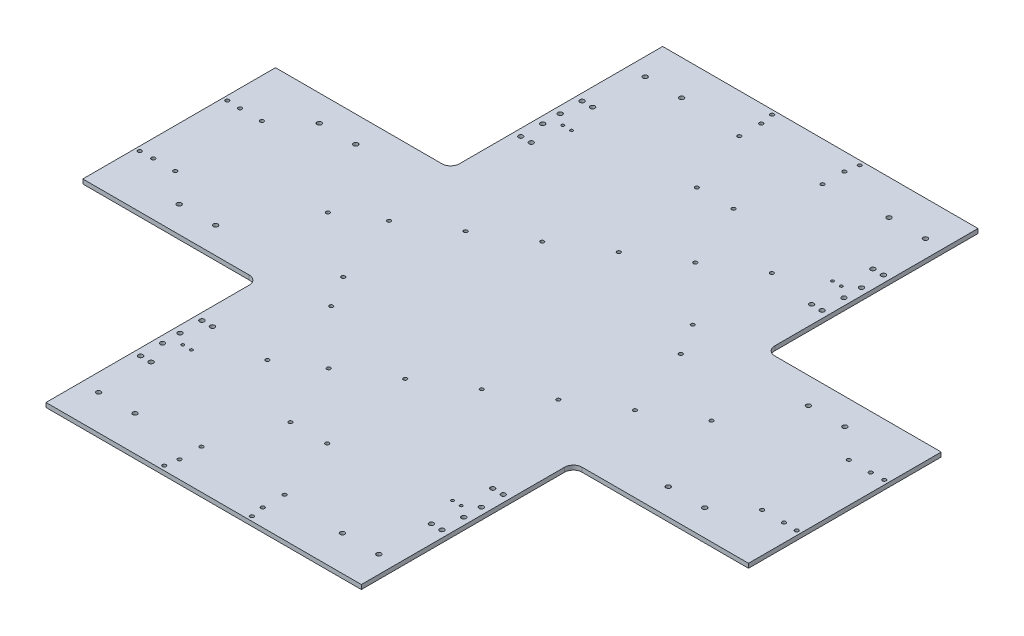
SolidWorks part; units mm, degrees
other "Markup1"
sketch "Sketch8"
material "3.0205 (EN-AW 1200)"
ref_plane "前视基准面" through (0, 0, 0) normal (0, 0, 1) x (1, 0, 0)
ref_plane "上视基准面" through (0, 0, 0) normal (0, 1, 0) x (1, 0, 0)
ref_plane "右视基准面" through (0, 0, 0) normal (1, 0, 0) x (0, 0, -1)
other "Configuration Table"
sketch "Sketch1" plane through (0, 0, 0) normal (0, 1, 0) x (1, 0, 0)
  line L0 (180, 352) -> (-180, 352)
  line L1 (-180, 352) -> (-180, 110)
  line L2 (-180, 110) -> (-380, 110)
  line L5 (-380, 110) -> (-380, -110)
  line L6 (0, 352) -> (0, -66.8675) construction
  line L7 (-380, 0) -> (131.0517, 0) construction
  line L8 (380, 110) -> (380, -110)
  line L11 (180, 110) -> (380, 110)
  line L12 (180, 352) -> (180, 110)
  line L13 (180, -352) -> (180, -110)
  line L14 (180, -110) -> (380, -110)
  line L19 (-180, -110) -> (-380, -110)
  line L20 (-180, -352) -> (-180, -110)
  line L21 (180, -352) -> (-180, -352)
  point P21 (380, 0)
  dimension "D1" = 180
  dimension "D2" = 200
  dimension "D3" = 110
  dimension "D4" = 242
extrude "Boss-Extrude1" add sketch "Sketch1" along normal blind 5
sketch "Sketch2" plane through (0, 5, 0) normal (0, 1, 0) x (1, 0, 0)
  line L3 (380, -110) -> (380, 110) construction
  line L4 (-56.7455, 0) -> (47.5165, 0) construction
  line L5 (0, 54.7142) -> (0, -64.2255) construction
  line L7 (180, 352) -> (-180, 352) construction
  circle A0 centre (360, 49.5) radius 2.125
  circle A1 centre (335, 49.5) radius 2.125
  circle A7 centre (335, -49.5) radius 2.125
  circle A8 centre (360, -49.5) radius 2.125
  circle A9 centre (-360, -49.5) radius 2.125
  circle A10 centre (-335, -49.5) radius 2.125
  circle A13 centre (-335, 49.5) radius 2.125
  circle A14 centre (-360, 49.5) radius 2.125
  circle A15 centre (47.5, 332) radius 2.125
  circle A16 centre (47.5, 307) radius 2.125
  circle A17 centre (-47.5, 307) radius 2.125
  circle A18 centre (-47.5, 332) radius 2.125
  circle A19 centre (-47.5, -332) radius 2.125
  circle A20 centre (-47.5, -307) radius 2.125
  circle A21 centre (47.5, -307) radius 2.125
  circle A22 centre (47.5, -332) radius 2.125
  dimension "D3" = 49.5
  dimension "D5" = 4.25
  dimension "D7" = 4.25
  dimension "D9" = 4.25
  dimension "D10" = 4.25
  dimension "D2" = 47.5
  dimension "D4" = 25
  dimension "D6" = 20
  dimension "20" = 20
  dimension "D13" = 25
extrude "Cut-Extrude1" cut sketch "Sketch2" against normal blind 3
sketch "Sketch4" plane through (0, 5, 0) normal (0, 1, 0) x (1, 0, 0)
  line L0 (-180, 352) -> (-180, 110) construction
  line L1 (180, 352) -> (-180, 352) construction
  line L2 (0, 46.9886) -> (0, -40.2904) construction
  line L3 (-35.103, 0) -> (92.4951, 0) construction
  line L5 (180, -352) -> (180, -110) construction
  circle A0 centre (-172, 182) radius 2.6
  circle A1 centre (-160, 182) radius 2.6
  circle A2 centre (-172, 207) radius 2.6
  circle A3 centre (-172, 227) radius 2.6
  circle A4 centre (-172, 252) radius 2.6
  circle A5 centre (-160, 252) radius 2.6
  circle A6 centre (160, 252) radius 2.6
  circle A7 centre (172, 252) radius 2.6
  circle A8 centre (172, 227) radius 2.6
  circle A9 centre (172, 207) radius 2.6
  circle A10 centre (160, 182) radius 2.6
  circle A11 centre (172, 182) radius 2.6
  circle A12 centre (172, -182) radius 2.6
  circle A13 centre (160, -182) radius 2.6
  circle A14 centre (172, -207) radius 2.6
  circle A15 centre (172, -227) radius 2.6
  circle A16 centre (172, -252) radius 2.6
  circle A17 centre (160, -252) radius 2.6
  circle A18 centre (-160, -252) radius 2.6
  circle A19 centre (-172, -252) radius 2.6
  circle A20 centre (-172, -227) radius 2.6
  circle A21 centre (-172, -207) radius 2.6
  circle A22 centre (-160, -182) radius 2.6
  circle A23 centre (-172, -182) radius 2.6
  circle A24 centre (159, -217) radius 1.6
  circle A25 centre (-159, -217) radius 1.6
  circle A26 centre (159, 217) radius 1.6
  circle A27 centre (-159, 217) radius 1.6
  circle A28 centre (149, -217) radius 1.6
  circle A29 centre (-149, -217) radius 1.6
  circle A30 centre (149, 217) radius 1.6
  circle A31 centre (-149, 217) radius 1.6
  dimension "D3" = 5.2
  dimension "D4" = 5.2
  dimension "D5" = 8
  dimension "D6" = 8
  dimension "D9" = 5.2
  dimension "D10" = 5.2
  dimension "D11" = 5.2
  dimension "D12" = 5.2
  dimension "D19" = 3.2
  dimension "D20" = 21
  dimension "D21" = 10
  dimension "D22" = 3.2
  dimension "D23" = 10
  dimension "D1" = 8
  dimension "D2" = 20
  dimension "D7" = 8
  dimension "D8" = 20
  dimension "D13" = 25
  dimension "D14" = 20
  dimension "D15" = 25
  dimension "D16" = 25
  dimension "D17" = 100
  dimension "D18" = 0
extrude "Cut-Extrude3" cut sketch "Sketch4" against normal blind 10
sketch "Sketch5" plane through (0, 5, 0) normal (0, 1, 0) x (1, 0, 0)
  line L0 (180, 352) -> (-180, 352) construction
  line L5 (-46.9195, 0) -> (66.6223, 0) construction
  line L6 (0, 59.0569) -> (0, -54.4849) construction
  line L10 (-380, 110) -> (-380, -110) construction
  circle A0 centre (-50, 347) radius 2.1
  circle A1 centre (50, 347) radius 2.1
  circle A2 centre (50, -347) radius 2.1
  circle A3 centre (-50, -347) radius 2.1
  circle A4 centre (-375, 50) radius 2.1
  circle A5 centre (-375, -50) radius 2.1
  circle A6 centre (375, -50) radius 2.1
  circle A7 centre (375, 50) radius 2.1
  dimension "D1" = 4.2
  dimension "D2" = 4.2
  dimension "D3" = 50
  dimension "D6" = 4.2
  dimension "D7" = 4.2
  dimension "5" = 5
  dimension "D4" = 50
  dimension "D5" = 50
  dimension "D8" = 50
  dimension "D9" = 5
  dimension "D10" = 5
extrude "Cut-Extrude4" cut sketch "Sketch5" against normal blind 10
fillet "Fillet1" radius 10 4 edges at (-180, 2.5, -110) (-180, 2.5, 110) (180, 2.5, 110) (180, 2.5, -110)
sketch "Sketch6" plane through (0, 5, 0) normal (0, 1, 0) x (1, 0, 0)
  line L0 (180, 352) -> (-180, 352) construction
  line L1 (-180, 352) -> (-180, 120) construction
  line L3 (0, 50.3702) -> (0, -42.7646) construction
  line L4 (-54.8568, 0) -> (91.2004, 0) construction
  line L5 (380, 110) -> (190, 110) construction
  line L6 (380, -110) -> (380, 110) construction
  circle A0 centre (-160, 312) radius 2.6
  circle A1 centre (-118.4, 312) radius 2.6
  circle A4 centre (118.4, 312) radius 2.6
  circle A5 centre (160, 312) radius 2.6
  circle A6 centre (160, -312) radius 2.6
  circle A7 centre (118.4, -312) radius 2.6
  circle A8 centre (-118.4, -312) radius 2.6
  circle A9 centre (-160, -312) radius 2.6
  circle A10 centre (258.4, 80) radius 2.6
  circle A11 centre (300, 80) radius 2.6
  circle A12 centre (300, -80) radius 2.6
  circle A13 centre (258.4, -80) radius 2.6
  circle A14 centre (-258.4, -80) radius 2.6
  circle A15 centre (-300, -80) radius 2.6
  circle A16 centre (-300, 80) radius 2.6
  circle A17 centre (-258.4, 80) radius 2.6
  dimension "D1" = 5.2
  dimension "D2" = 5.2
  dimension "D3" = 5.2
  dimension "D4" = 5.2
  dimension "D5" = 40
  dimension "D8" = 30
  dimension "D6" = 20
  dimension "D7" = 41.6
  dimension "D9" = 80
  dimension "D10" = 41.6
extrude "Cut-Extrude5" cut sketch "Sketch6" against normal blind 10
sketch "Sketch7" plane through (0, 5, 0) normal (0, 1, 0) x (1, 0, 0)
  line L0 (182.9289, 112.9289) -> (-182.9289, -112.9289) construction
  line L1 (180, 235.6925) -> (-379.973, -110) construction
  line L2 (180, 120) -> (180, 352) construction
  line L3 (-380, -110) -> (-190, -110) construction
  line L4 (379.973, 110) -> (-180, -235.6925) construction
  line L5 (380, 110) -> (190, 110) construction
  line L6 (-180, -120) -> (-180, -352) construction
  line L7 (-252.1038, -38.9487) -> (-83.0161, -312.847) construction
  line L8 (99.6992, 266.786) -> (288.8891, -39.6749) construction
  line L9 (-55.682, 90.1971) -> (55.682, -90.1971) construction
  arc A0 (180, 120) -> (190, 110) centre (190, 120) ccw construction
  arc A1 (-180, -120) -> (-190, -110) centre (-190, -120) ccw construction
  circle A4 centre (-55.682, 90.1971) radius 2.1
  circle A5 centre (-1.6489, 123.5538) radius 2.1
  circle A6 centre (52.3842, 156.9105) radius 2.1
  circle A7 centre (106.4174, 190.2672) radius 2.1
  circle A8 centre (-109.7152, 56.8404) radius 2.1
  circle A9 centre (-163.7483, 23.4837) radius 2.1
  circle A10 centre (-206.9749, -3.2017) radius 2.1
  circle A11 centre (-95.6108, -183.5958) radius 2.1
  circle A12 centre (-52.3842, -156.9105) radius 2.1
  circle A13 centre (1.6489, -123.5538) radius 2.1
  circle A14 centre (217.7815, 9.873) radius 2.1
  circle A15 centre (163.7483, -23.4837) radius 2.1
  circle A16 centre (109.7152, -56.8404) radius 2.1
  circle A17 centre (55.682, -90.1971) radius 2.1
  dimension "D6" = 4.2
  dimension "D7" = 4.2
  dimension "D8" = 4.2
  dimension "D9" = 4.2
  dimension "D10" = 4.2
  dimension "D11" = 4.2
  dimension "D12" = 4.2
  dimension "D1" = 106
  dimension "D3" = 20
  dimension "D4" = 20
  dimension "D5" = 0
  dimension "D13" = 63.5
  dimension "D14" = 63.5
  dimension "D15" = 50.8
  dimension "D16" = 63.5
  dimension "D17" = 63.5
  dimension "D18" = 63.5
extrude "Cut-Extrude6" cut sketch "Sketch7" against normal blind 10
sketch "Sketch9" plane through (0, 5, 0) normal (0, 1, 0) x (1, 0, 0)
  line L0 (182.9289, 112.9289) -> (-182.9289, -112.9289) construction
  line L1 (92.6836, 125.8571) -> (158.1979, 19.7331) construction
  line L2 (-151.014, -31.37) -> (-99.0832, -115.4905) construction
  line L3 (0, 45.0584) -> (0, -52.9183) construction
  line L4 (-44.6513, 0) -> (48.0404, 0) construction
  line L5 (180, 352) -> (-180, 352) construction
  arc A0 (180, 120) -> (190, 110) centre (190, 120) ccw construction
  arc A1 (-180, -120) -> (-190, -110) centre (-190, -120) ccw construction
  circle A2 centre (-134.3962, -58.2885) radius 2.1
  circle A3 centre (-112.3335, -94.027) radius 2.1
  circle A4 centre (112.3335, 94.027) radius 2.1
  circle A5 centre (134.3962, 58.2885) radius 2.1
  circle A7 centre (21, 232) radius 2.1
  circle A8 centre (-21, 232) radius 2.1
  circle A9 centre (-21, -232) radius 2.1
  circle A10 centre (21, -232) radius 2.1
  dimension "D3" = 4.2
  dimension "D4" = 4.2
  dimension "D5" = 4.2
  dimension "D6" = 4.2
  dimension "D11" = 120
  dimension "D12" = 4.2
  dimension "D1" = 70
  dimension "D2" = 70
  dimension "D7" = 21
  dimension "D8" = 21
  dimension "D9" = 21
  dimension "D10" = 21
  dimension "D13" = 21
extrude "Cut-Extrude7" cut sketch "Sketch9" against normal blind 10
